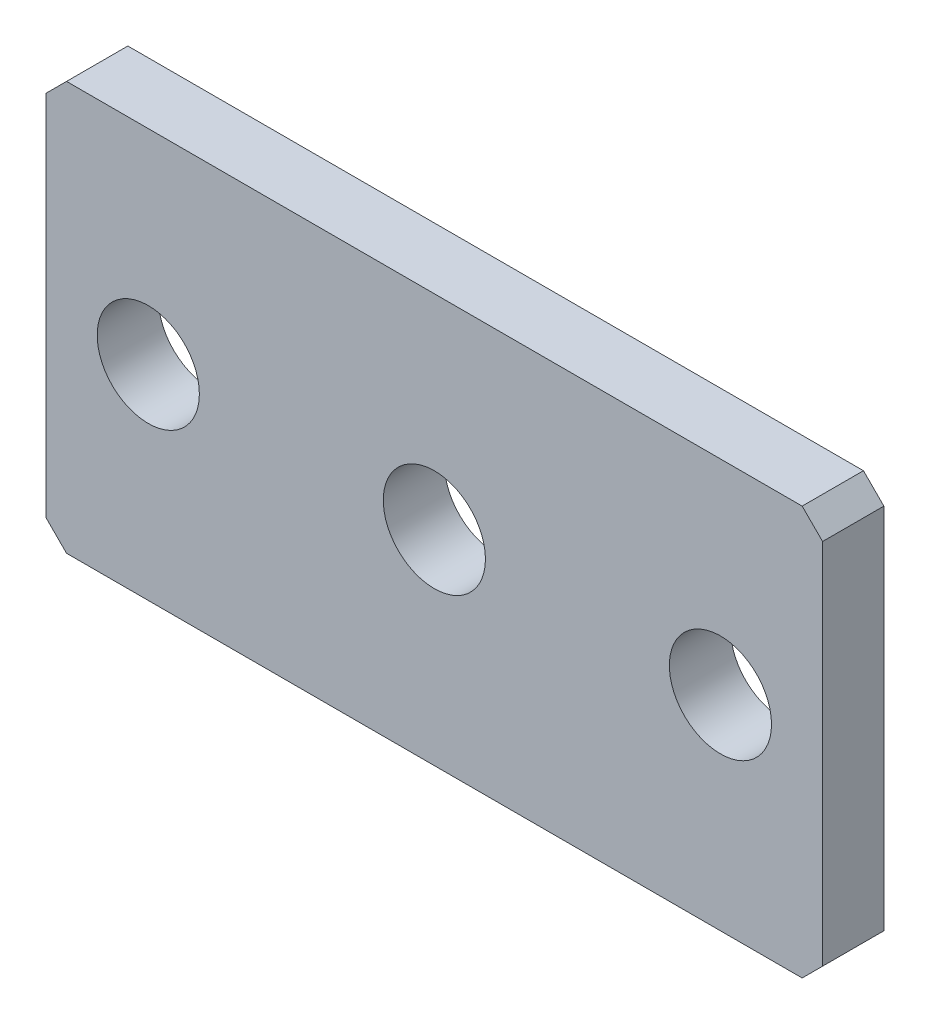
SolidWorks part; units mm, degrees
ref_plane "前视基准面" through (0, 0, 0) normal (0, 0, 1) x (1, 0, 0)
ref_plane "上视基准面" through (0, 0, 0) normal (0, 1, 0) x (1, 0, 0)
ref_plane "右视基准面" through (0, 0, 0) normal (1, 0, 0) x (0, 0, -1)
sketch "草图1" plane through (0, 0, 0) normal (0, 0, 1) x (1, 0, 0)
  line L0 (0, 10) -> (0, -10) construction
  line L1 (-18, 10) -> (18, 10)
  line L2 (-19, 9) -> (-19, -9)
  line L3 (-18, -10) -> (18, -10)
  line L4 (19, 9) -> (19, -9)
  line L5 (-19, 10) -> (19, -10) construction
  line L6 (-19, -10) -> (19, 10) construction
  line L7 (-20, 0) -> (24, 0) construction
  line L8 (-18, 10) -> (-19, 9)
  line L9 (18, 10) -> (19, 9)
  line L10 (19, -9) -> (18, -10)
  line L11 (-19, -9) -> (-18, -10)
  circle A0 centre (-14, 0) radius 2.5
  circle A1 centre (14, 0) radius 2.5
  point P0 (0, 0)
  dimension "D4" = 5
  dimension "D5" = 20
  dimension "D6" = 10
  dimension "D2" = 38
  dimension "D3" = 28
base flange "基体-法兰1" sketch "草图1" thickness 3 reverse thickness direction no parameters "D1"=0.5
hole_wizard "M6 螺纹孔1" positions "草图7" profile "草图6" tap size "M6" standard "GB"
sketch "草图7" plane through (0, 0, 0) normal (0, 0, 1) x (1, 0, 0)
  point P0 (0, 0)
sketch "草图6" plane through (0, 0, 0) normal (1, 0, 0) x (0, -1, 0)
  line L0 (0, 0) -> (0, 20.5022)
  line L1 (0, 20.5022) -> (2.5, 19)
  line L2 (2.5, 19) -> (2.5, 0)
  line L5 (2.5, 0) -> (0, 0)
  line L10 (0, 20.5022) -> (-2.5, 19) construction
  line L11 (0, -6.35) -> (0, 107.95) construction
  dimension "螺纹孔钻头直径" = 5
  dimension "螺纹孔钻头深度" = 19
  dimension "导头角度" = 118
cosmetic thread "孔螺蚊线1"
sketch "折弯-线1" plane through (0, 0, 0) normal (0, 1, 0) x (1, 0, 0)
sketch "边界框1" plane through (0, 0, 0) normal (0, 1, 0) x (1, 0, 0)
sheet metal parameters "钣金1" thickness 3 parameters "D1"=0.5
flat pattern "平板型式1" [suppressed]
sketch "折弯-线2" plane through (0, 0, 0) normal (0, 1, 0) x (1, 0, 0)
sketch "边界框2" [suppressed] plane through (0, 0, 0) normal (0, 1, 0) x (1, 0, 0)
sheet metal parameters "钣金2" thickness 3 parameters "D1"=0.5
flat pattern "平板型式1"
sketch "折弯-线2" plane through (0, 0, 0) normal (0, 1, 0) x (1, 0, 0)
sketch "边界框2" [suppressed] plane through (0, 0, 0) normal (0, 1, 0) x (1, 0, 0)
